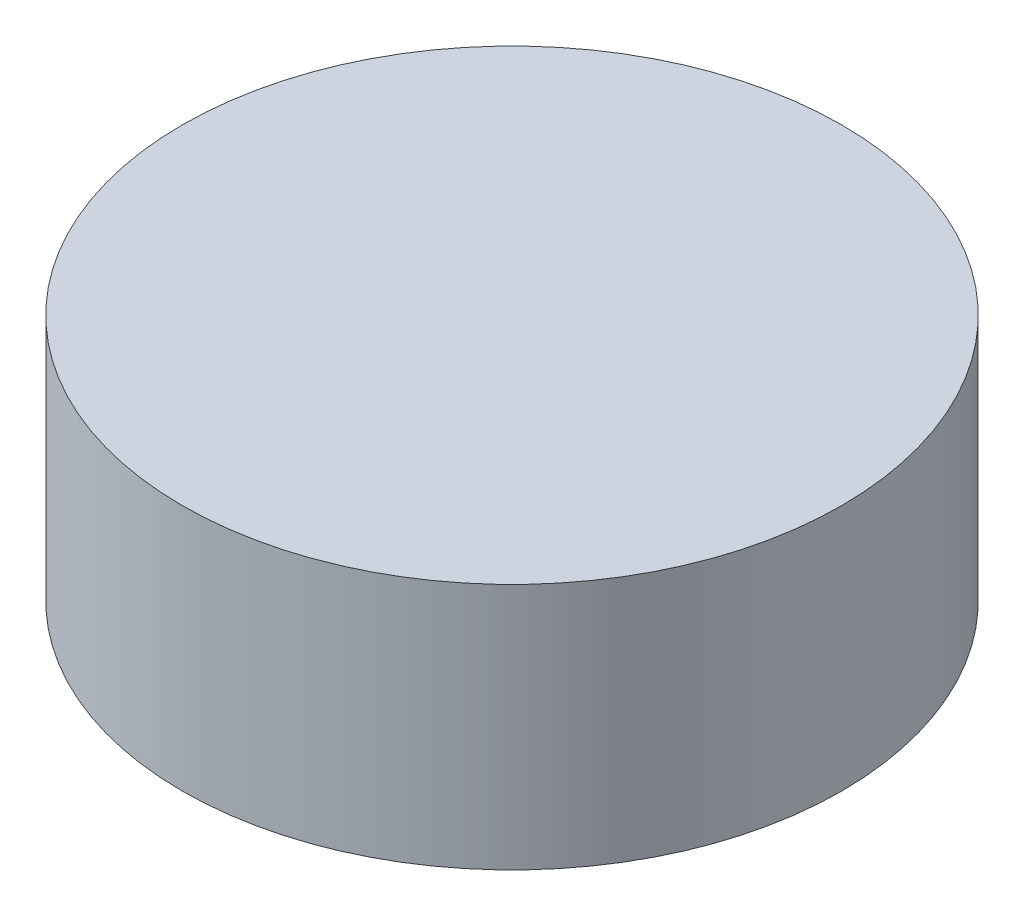
SolidWorks part; units mm, degrees
ref_plane "Top Plane" through (0, 0, 0) normal (0, 0, 1) x (1, 0, 0)
ref_plane "Right Plane" through (0, 0, 0) normal (0, 1, 0) x (1, 0, 0)
ref_plane "Front Plane" through (0, 0, 0) normal (1, 0, 0) x (0, 0, -1)
ref_axis "x-axis" through (-88.99, 0, 0) along (1, 0, 0)
ref_axis "y-axis" through (0, -55, 0) along (0, 1, 0)
ref_axis "z-axis" through (0, 0, 55) along (0, 0, -1)
sketch "Sketch1" plane through (0, 0, 0) normal (0, 1, 0) x (1, 0, 0)
  circle A0 centre (0, 0) radius 4
  dimension "D1" = 8
extrude "Boss-Extrude1" add sketch "Sketch1" against normal blind 3
